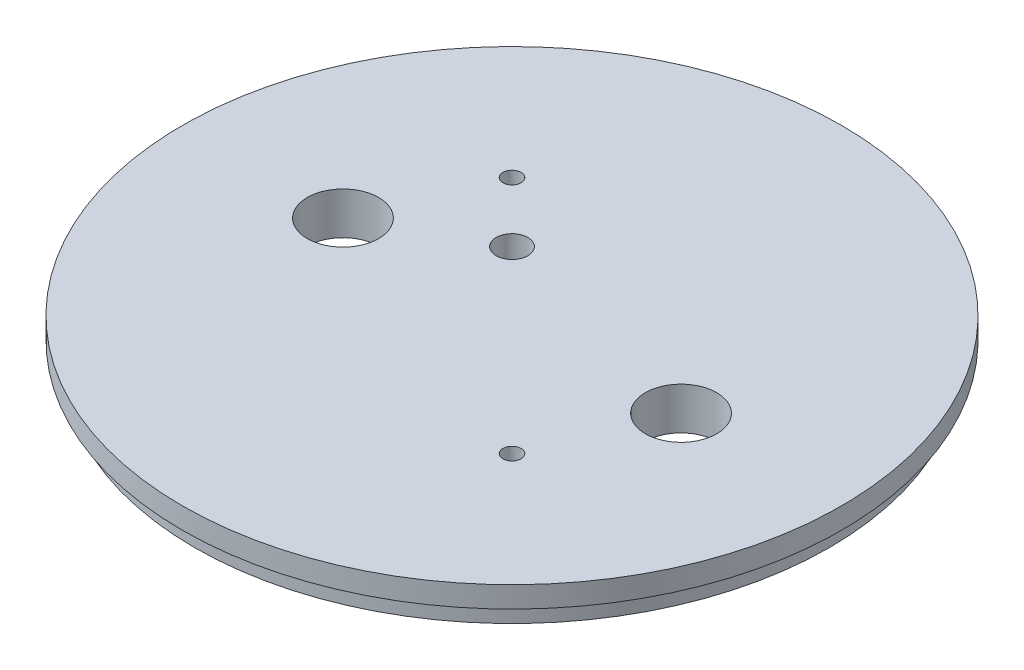
SolidWorks part; units mm, degrees
material "6061-T4 (SS)"
ref_plane "Front Plane" through (0, 0, 0) normal (0, 0, 1) x (1, 0, 0)
ref_plane "Top Plane" through (0, 0, 0) normal (0, 1, 0) x (1, 0, 0)
ref_plane "Right Plane" through (0, 0, 0) normal (1, 0, 0) x (0, 0, -1)
sketch "Sketch1" plane through (0, 0, 0) normal (0, 1, 0) x (1, 0, 0)
  line L0 (0, -49.5173) -> (0, 49.5173) construction
  line L1 (-49.5173, 0) -> (49.5173, 0) construction
  line L2 (-17.9605, 17.9605) -> (0, 0) construction
  line L3 (0, 56.7387) -> (0, 29.6936) construction
  line L4 (3.6407, 56.7387) -> (3.6407, 29.6936) construction
  line L5 (-3.6407, 56.7387) -> (-3.6407, 29.6936) construction
  line L6 (0, -56.7387) -> (0, -29.6936) construction
  line L7 (3.6407, -56.7387) -> (3.6407, -29.6936) construction
  line L8 (-3.6407, -56.7387) -> (-3.6407, -29.6936) construction
  line L9 (-35.014, -35.014) -> (54.3236, 54.3236) construction
  circle A0 centre (0, 0) radius 49.5173
  circle A1 centre (0, 0) radius 3.175 construction
  circle A2 centre (25.4, 0) radius 5.3578
  circle A3 centre (-25.4, 0) radius 5.3578
  circle A4 centre (-17.9605, 17.9605) radius 1.3589
  arc A6 (3.6407, 56.7387) -> (-3.6407, 56.7387) centre (0, 56.7387) ccw construction
  arc A7 (-3.6407, 29.6936) -> (3.6407, 29.6936) centre (0, 29.6936) ccw construction
  arc A8 (3.6407, -56.7387) -> (-3.6407, -56.7387) centre (0, -56.7387) cw construction
  arc A9 (-3.6407, -29.6936) -> (3.6407, -29.6936) centre (0, -29.6936) cw construction
  circle A10 centre (17.9605, -17.9605) radius 1.3589
  circle A11 centre (-8.9803, 8.9803) radius 2.3813
  circle A12 centre (8.9803, -8.9803) radius 2.3813 construction
  point P16 (0, 43.2162)
  point P19 (0, 0)
  point P26 (0, -43.2162)
  dimension "D1" = 99.0346
  dimension "D2" = 6.35
  dimension "D3" = 10.7156
  dimension "D5" = 2.7178
  dimension "D8" = 4.7625
  dimension "D6" = 25.4
  dimension "D7" = 45
  dimension "D4" = 45
  dimension "D9" = 25.4
extrude "Boss-Extrude1" add sketch "Sketch1" along normal blind 6.35
sketch "Sketch2" plane through (0, 0, 0) normal (0, -1, 0) x (1, 0, 0)
  circle A0 centre (0, 0) radius 49.5173
  circle A1 centre (0, 0) radius 47.6885
  dimension "D1" = 99.0346
  dimension "D2" = 95.377
extrude "Cut-Extrude1" cut sketch "Sketch2" against normal blind 3.175
sketch "Sketch3" plane through (0, 6.35, 0) normal (0, 1, 0) x (1, 0, 0)
  line L0 (0, 49.5173) -> (0, -49.5173) construction
  line L1 (-49.5173, 0) -> (49.5173, 0) construction
  line L2 (0, 34.798) -> (0, 13.97) construction
  line L3 (3.2385, 34.798) -> (3.2385, 13.97)
  line L4 (-3.2385, 34.798) -> (-3.2385, 13.97)
  line L5 (0, -34.798) -> (0, -13.97) construction
  line L6 (3.2385, -34.798) -> (3.2385, -13.97)
  line L7 (-3.2385, -34.798) -> (-3.2385, -13.97)
  circle A0 centre (0, 0) radius 49.5173 construction
  arc A1 (3.2385, 34.798) -> (-3.2385, 34.798) centre (0, 34.798) ccw
  arc A2 (-3.2385, 13.97) -> (3.2385, 13.97) centre (0, 13.97) ccw
  arc A3 (3.2385, -34.798) -> (-3.2385, -34.798) centre (0, -34.798) cw
  arc A4 (-3.2385, -13.97) -> (3.2385, -13.97) centre (0, -13.97) cw
  point P7 (0, 13.97)
  point P8 (0, 34.798)
  point P12 (0, 24.384)
  point P20 (0, -24.384)
  point P25 (0, -34.798)
  point P26 (0, -13.97)
  dimension "D1" = 13.97
  dimension "D2" = 20.828
  dimension "D3" = 6.477
extrude "Cut-Extrude2" cut sketch "Sketch3" against normal blind 3.81 from offset 2.794 offset against normal yes
equation "\"Coupler_OD\" = 3.899in"
equation "\"Coupler_ID\" = 3.755in"
equation "\"Lead_Screw_Hole_Diam\" = (27/64)*1in"
equation "\"Lead_Screw_Dist\" = 2in"
equation "\"D9@Sketch1\"=\"Lead_Screw_Dist\"/2"
equation "\"D3@Sketch1\"=\"Lead_Screw_Hole_Diam\""
equation "\"Body_Tube_OD\"= 4.024in"
equation "\"Body_Tube_ID\"= 3.90in"
equation "\"Avionics_Bulkhead_Thickness\" = 0.25in"
equation "\"Avionics_Bulkhead_Lip\" = 0.125in"
equation "\"Lead_Screw_Diam\" = 0.375in"
equation "\"D1@Sketch2\"=\"Coupler_OD\""
equation "\"D2@Sketch2\"=\"Coupler_ID\""
equation "\"D1@Sketch1\"=\"Coupler_OD\""
equation "\"D1@Boss-Extrude1\"=\"Avionics_Bulkhead_Thickness\""
equation "\"D1@Cut-Extrude1\"=\"Avionics_Bulkhead_Lip\""
